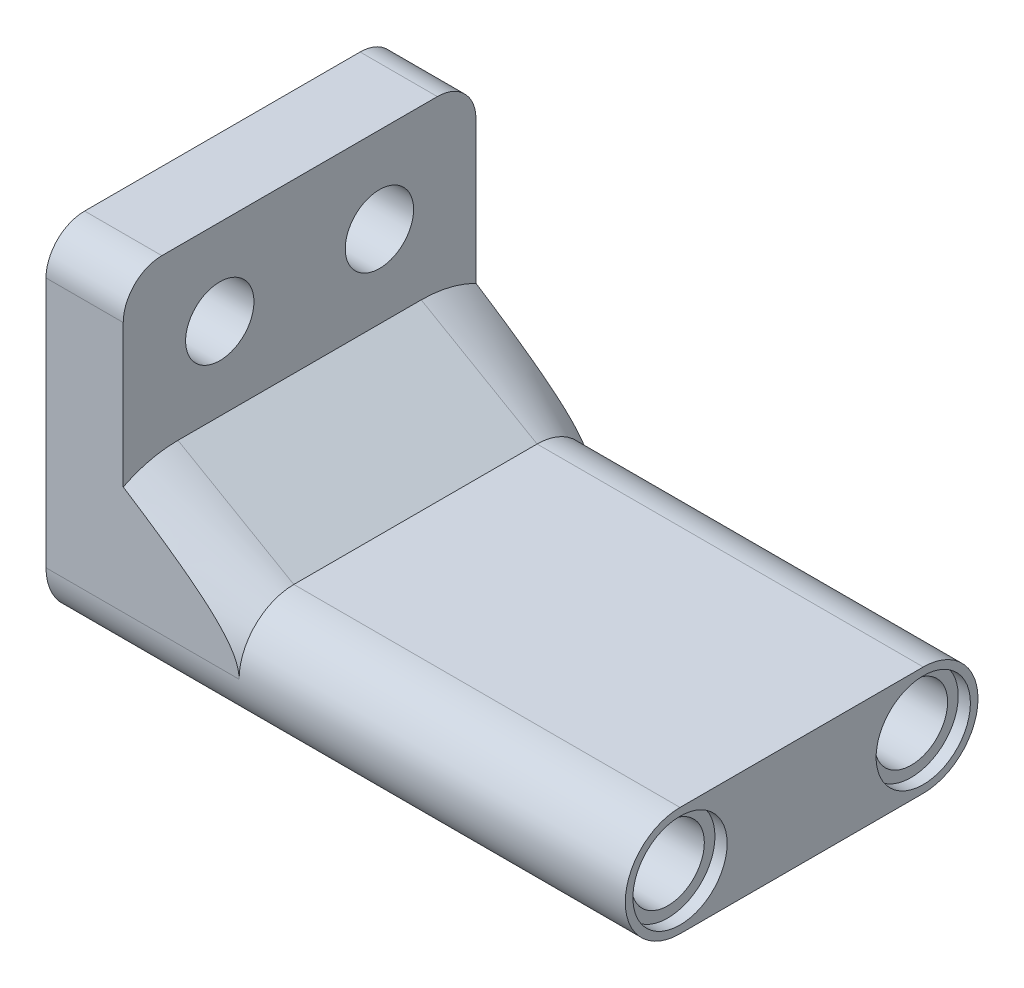
SolidWorks part; units mm, degrees
ref_plane "Front Plane" through (0, 0, 0) normal (0, 0, 1) x (1, 0, 0)
ref_plane "Top Plane" through (0, 0, 0) normal (0, 1, 0) x (1, 0, 0)
ref_plane "Right Plane" through (0, 0, 0) normal (1, 0, 0) x (0, 0, -1)
sketch "Sketch1" plane through (0, 0, 0) normal (1, 0, 0) x (0, 0, -1)
  line L1 (0, 0) -> (-16, 0)
  line L3 (0, 7.2) -> (-16, 7.2)
  arc A0 (0, 0) -> (0, 7.2) centre (0, 3.6) ccw
  arc A1 (-16, 7.2) -> (-16, 0) centre (-16, 3.6) ccw
  point P0 (-19.6, 3.6)
  point P2 (3.6, 3.6)
  dimension "D1" = 23.2
  dimension "D2" = 7.2
extrude "Boss-Extrude1" add sketch "Sketch1" along normal blind 38.1
sketch "Sketch2" plane through (38.1, 0, 0) normal (1, 0, 0) x (0, 0, -1)
  line L0 (-8, 7.2) -> (-8, 0) construction
  line L1 (0, 7.2) -> (-16, 7.2) construction
  line L2 (-16, 0) -> (0, 0) construction
  circle A0 centre (-16, 3.6) radius 2.4
  circle A1 centre (0, 3.6) radius 2.4
  arc A2 (-16, 7.2) -> (-16, 0) centre (-16, 3.6) ccw construction
  arc A3 (0, 0) -> (0, 7.2) centre (0, 3.6) ccw construction
  circle A4 centre (-16, 3.6) radius 3.1
  circle A5 centre (0, 3.6) radius 3.1
  point P7 (-19.6, 3.6)
  point P11 (3.6, 3.6)
  point P19 (-8, 3.6)
  dimension "D3" = 4.8
  dimension "D4" = 4.8
  dimension "D5" = 6.2
  dimension "D6" = 6.2
  dimension "D1" = 3.6
  dimension "D2" = 3.6
extrude "Cut-Extrude1" cut sketch "Sketch2" against normal blind 8 contours A1 | A0 region at (38.1, 3.6, 0)
extrude "Cut-Extrude2" cut sketch "Sketch2<3>" against normal blind 0.8 contours A5 A1 | A4 A0 region at (38.1, 3.6, 19.0123) region at (38.1, 3.6, 3.0123)
sketch "Sketch2<3>" plane through (38.1, 0, 0) normal (1, 0, 0) x (0, 0, -1) same geometry as "Sketch2"
ref_plane "Plane1" through (34.1, 0, 0) normal (1, 0, 0) x (0, 0, -1)
sketch "Sketch3" plane through (30.1, 0, 0) normal (1, 0, 0) x (0, 0, -1)
  circle A0 centre (-16, 3.6) radius 3.1
  circle A1 centre (0, 3.6) radius 3.1
  dimension "D1" = 6.2
  dimension "D2" = 6.2
extrude "Cut-Extrude3" cut sketch "Sketch3" against normal blind 1.5
ref_plane "Plane2" through (0, 3.6, 0) normal (0, 1, 0) x (1, 0, 0)
sketch "Sketch4" plane through (0, 3.6, 0) normal (0, 1, 0) x (1, 0, 0)
  line L0 (0, -19.6) -> (38.1, -19.6) construction
  line L1 (0, 3.6) -> (5.08, 3.6)
  line L2 (0, 3.6) -> (0, -19.6)
  line L3 (0, -19.6) -> (5.08, -19.6)
  line L4 (5.08, 3.6) -> (5.08, -19.6)
  dimension "D1" = 5.08
extrude "Boss-Extrude2" add sketch "Sketch4" along normal blind 19.05
fillet "Fillet1" radius 2.54 2 edges at (2.54, 22.65, 19.6) (2.54, 22.65, -3.6)
chamfer "Chamfer1" distance 7.62 angle 30 3 edges at (5.08, 6.1456, 18.5456) (5.08, 6.1456, -2.5456) (5.08, 7.2, 8) first distance on face at (14.3933, 3.6, 18.0485) first distance on face at (14.3933, 3.6, -2.0485) first distance on face at (21.59, 7.2, 8)
sketch "Sketch5" plane through (5.08, 0, 0) normal (1, 0, 0) x (0, 0, -1)
  line L1 (-19.6, 20.11) -> (-19.6, 10.7436) construction
  line L2 (3.6, 20.11) -> (3.6, 10.7436) construction
  circle A0 centre (-13.25, 17.0069) radius 1.5875
  circle A1 centre (-2.75, 17.0069) radius 1.5875
  dimension "D2" = 3.175
  dimension "D3" = 3.175
  dimension "D1" = 6.35
  dimension "D4" = 6.35
hole_wizard "#8 Clearance Hole1" positions "Sketch6" profile "Sketch7" hole size "#8" standard "ANSI Inch" end condition through all
sketch "Sketch6" plane through (5.08, 0, 0) normal (1, 0, 0) x (0, 0, -1)
  point P0 (-13.25, 17.0069)
  point P3 (-2.75, 17.0069)
sketch "Sketch7" plane through (5.08, 17.0069, 13.25) normal (0, 1, 0) x (0, 0, -1)
  line L0 (0, 0) -> (0, 5.08)
  line L1 (0, 5.08) -> (2.2479, 5.08)
  line L2 (2.2479, 5.08) -> (2.2479, 0)
  line L5 (2.2479, 0) -> (0, 0)
  line L11 (0, -6.35) -> (0, 107.95) construction
  dimension "Thru Hole Dia." = 4.4958
  dimension "Thru Hole Depth" = 5.08
